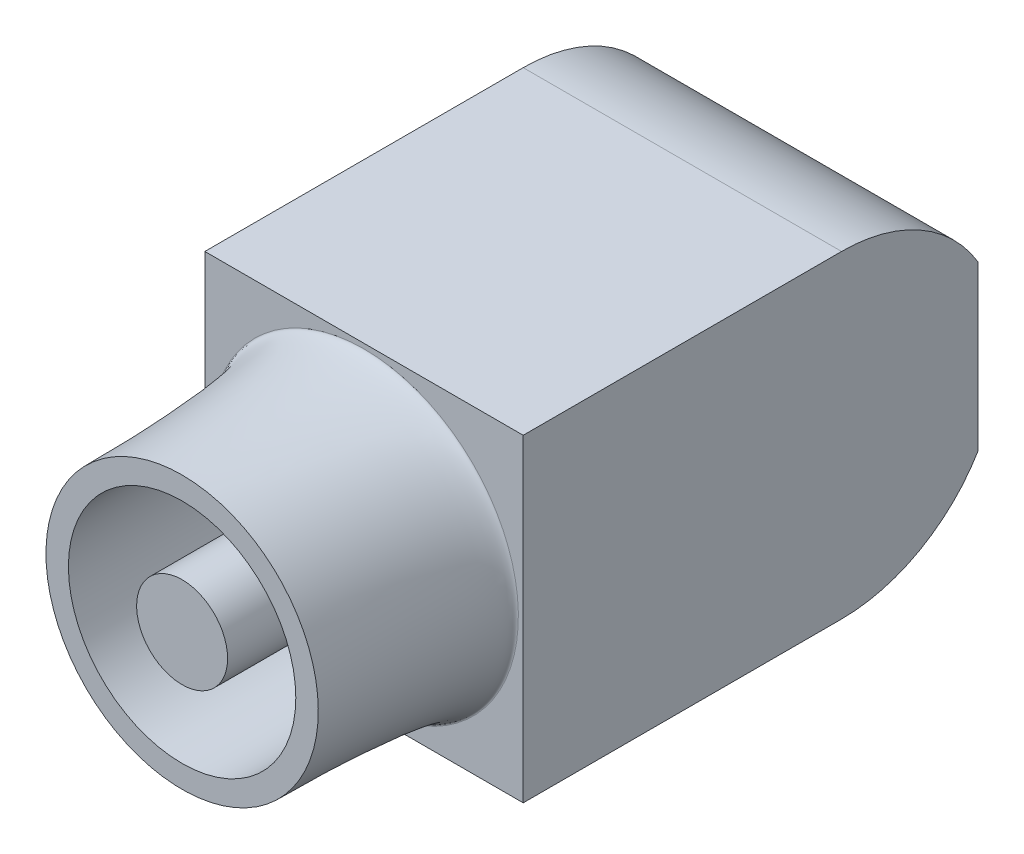
SolidWorks part; units mm, degrees
ref_plane "Ebene vorne" through (0, 0, 0) normal (0, 0, 1) x (1, 0, 0)
ref_plane "Ebene oben" through (0, 0, 0) normal (0, 1, 0) x (1, 0, 0)
ref_plane "Ebene rechts" through (0, 0, 0) normal (1, 0, 0) x (0, 0, -1)
sketch "Skizze2" plane through (0, 0, 0) normal (1, 0, 0) x (0, 0, -1)
  line L1 (15, 17.5) -> (-35, 17.5)
  line L2 (15, 17.5) -> (15, -17.5)
  line L3 (15, -17.5) -> (-35, -17.5)
  line L4 (-35, 17.5) -> (-35, -17.5)
  circle A0 centre (0, 0) radius 17.5
  dimension "D1" = 50
  dimension "D2" = 35
  dimension "D3" = 17.5
  dimension "D4" = 17.5
  dimension "D5" = 15
extrude "Aufsatz-Linear austragen1" add sketch "Skizze2" along normal blind 35 contours A0 | A0 L1 L4 L3 region at (0, 0, 24.0134) region at (0, 0, 0.5241)
sketch "Skizze3" plane through (0, 0, 35) normal (0, 0, 1) x (1, 0, 0)
  line L0 (0, 17.5) -> (0, -17.5) construction
  line L1 (35, 17.5) -> (0, 17.5) construction
  circle A0 centre (17.5, 0) radius 14.9699
  circle A1 centre (17.5, 0) radius 12.5
  circle A2 centre (17.5, 0) radius 5
  dimension "D2" = 17.5
  dimension "D1" = 17.5
extrude "Aufsatz-Linear austragen2" add sketch "Skizze3" along normal blind 20 contours A0 A1 | A2 region at (2.9535, 0, 35) region at (17.5, 0, 35)
fillet "Verrundung1" radius 2 1 edges at (17.5, 14.9699, 35) second distance 20 first distance on face at (17.5, 14.9699, 35)
sketch "Skizze4" plane through (0, 0, 0) normal (-1, 0, 0) x (0, 0, 1)
  circle A0 centre (0, 0) radius 5
extrude "Aufsatz-Linear austragen3" add sketch "Skizze4" along normal blind 2
